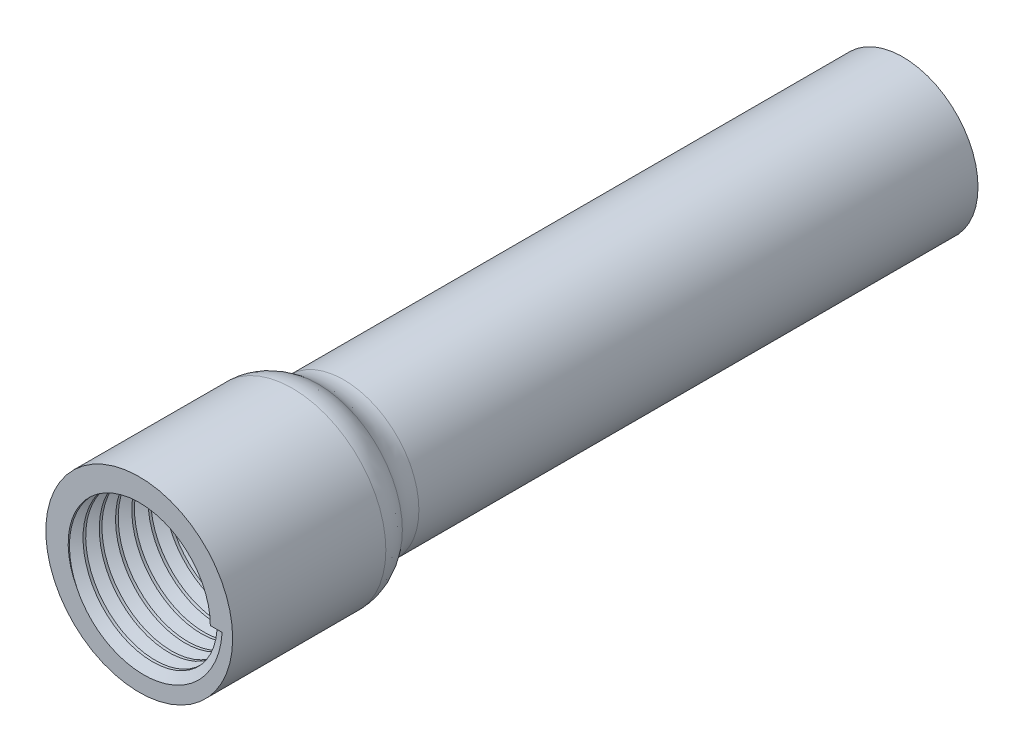
SolidWorks part; units mm, degrees
ref_plane "Front Plane" through (0, 0, 0) normal (0, 0, 1) x (1, 0, 0)
ref_plane "Top Plane" through (0, 0, 0) normal (0, 1, 0) x (1, 0, 0)
ref_plane "Right Plane" through (0, 0, 0) normal (1, 0, 0) x (0, 0, -1)
sketch "Sketch1" plane through (0, 0, 0) normal (0, 0, 1) x (1, 0, 0)
  circle A0 centre (0, 0) radius 6.5
  circle A1 centre (0, 0) radius 9.25
  dimension "D1" = 18.5
  dimension "D2" = 13
extrude "Boss-Extrude1" add sketch "Sketch1" along normal blind 74
sketch "Sketch6" plane through (0, 0, 74) normal (0, 0, 1) x (1, 0, 0)
  circle A0 centre (0, 0) radius 11.5
  circle A1 centre (0, 0) radius 8.75
  dimension "D1" = 23
  dimension "D2" = 17.5
extrude "Boss-Extrude2" add sketch "Sketch6" along normal blind 20 and the other way blind 1
sketch "Sketch2" plane through (0, 0, 94) normal (0, 0, 1) x (1, 0, 0)
  circle A0 centre (0, 0) radius 9.25
  dimension "D1" = 18.5
curve "Helix/Spiral1" pitch 2 height 20 turns 10
sketch "Sketch5" plane through (0, 0, 0) normal (0, 1, 0) x (1, 0, 0)
  line L1 (-11.5, -74.394) -> (11.5, -74.394) construction
  line L2 (-9.25, -70.6135) -> (9.25, -70.6135) construction
  line L3 (-9.25, 0) -> (-9.25, -73) construction
  line L4 (9.25, -73) -> (9.25, 0) construction
  line L5 (7.77, -92.597) -> (7.77, -95.403)
  line L6 (7.77, -95.403) -> (10.2, -94)
  line L8 (10.2, -94) -> (7.77, -92.597)
  line L9 (-11.5, -94) -> (11.5, -94) construction
  line L12 (-11.5, -73) -> (-11.5, -94) construction
  line L13 (11.5, -94) -> (11.5, -73) construction
  line L14 (0, -74.394) -> (0, -71.5957) construction
  point P1 (7.77, -94)
  dimension "D1" = 60
  dimension "D2" = 10.2
  dimension "D3" = 7.77
sweep "Cut-Sweep4" cut profiles "Sketch5" path "Helix/Spiral1"
fillet "Fillet2" radius 5 1 edges at (9.25, 0, 73)
fillet "Fillet3" radius 5 1 edges at (11.5, 0, 73)
